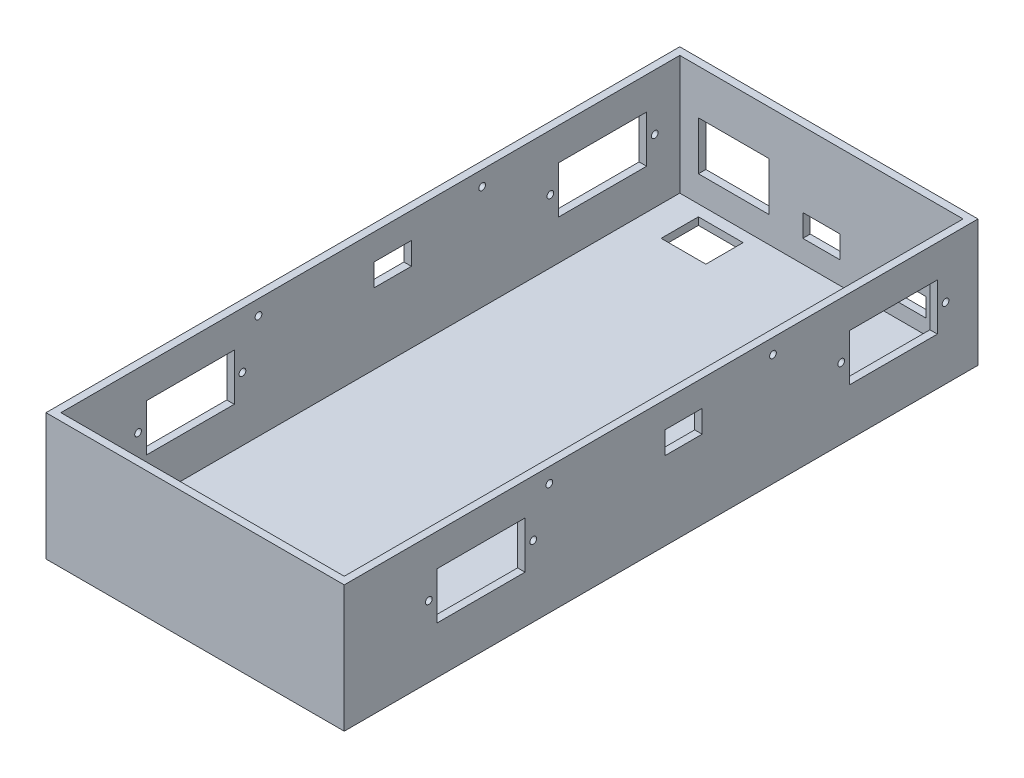
SolidWorks part; units mm, degrees
ref_plane "Front Plane" through (0, 0, 0) normal (0, 0, 1) x (1, 0, 0)
ref_plane "Top Plane" through (0, 0, 0) normal (0, 1, 0) x (1, 0, 0)
ref_plane "Right Plane" through (0, 0, 0) normal (1, 0, 0) x (0, 0, -1)
sketch "Sketch1" plane through (0, 0, 0) normal (0, 0, 1) x (1, 0, 0)
  line L1 (-40, 0) -> (40, 0)
  line L2 (-40, 0) -> (-40, 34)
  line L3 (-40, 34) -> (40, 34)
  line L4 (40, 0) -> (40, 34)
extrude "Boss-Extrude1" add sketch "Sketch1" along normal blind 170 from offset 85 offset against normal yes
sketch "Sketch2" plane through (0, 0, 0) normal (0, 0, 1) x (1, 0, 0)
  line L1 (-38, 2) -> (38, 2)
  line L2 (-38, 2) -> (-38, 40)
  line L3 (-38, 40) -> (38, 40)
  line L4 (38, 2) -> (38, 40)
extrude "Boss-Extrude2" add sketch "Sketch2" along normal blind 166 from offset 83 separate body offset against normal yes
combine bodies "Combine1" operation type subtract main body 101 bodies to subtract 102
sketch "Sketch3" plane through (0, 0, 0) normal (1, 0, 0) x (0, 0, -1)
  line L1 (-36.5, 12.7) -> (-60.1, 12.7)
  line L2 (-36.5, 12.7) -> (-36.5, 25.3)
  line L3 (-36.5, 25.3) -> (-60.1, 25.3)
  line L4 (-60.1, 12.7) -> (-60.1, 25.3)
extrude "Boss-Extrude3" add sketch "Sketch3" along normal blind 90 from offset 45 separate body offset against normal yes
combine bodies "Combine2" operation type subtract main body 103 bodies to subtract 104
sketch "Sketch4" plane through (0, 0, 0) normal (1, 0, 0) x (0, 0, -1)
  circle A0 centre (-34.3, 19) radius 0.9
extrude "Boss-Extrude4" add sketch "Sketch4" along normal blind 90 from offset 45 separate body offset against normal yes
combine bodies "Combine3" operation type subtract main body 105 bodies to subtract 106
sketch "Sketch5" plane through (0, 0, 0) normal (1, 0, 0) x (0, 0, -1)
  circle A0 centre (-62.3, 19) radius 0.9
extrude "Boss-Extrude5" add sketch "Sketch5" along normal blind 90 from offset 45 separate body offset against normal yes
combine bodies "Combine4" operation type subtract main body 107 bodies to subtract 108
sketch "Sketch6" plane through (0, 0, 0) normal (1, 0, 0) x (0, 0, -1)
  line L1 (74.1, 12.7) -> (50.5, 12.7)
  line L2 (74.1, 12.7) -> (74.1, 25.3)
  line L3 (74.1, 25.3) -> (50.5, 25.3)
  line L4 (50.5, 12.7) -> (50.5, 25.3)
extrude "Boss-Extrude6" add sketch "Sketch6" along normal blind 90 from offset 45 separate body offset against normal yes
combine bodies "Combine5" operation type subtract main body 109 bodies to subtract 110
sketch "Sketch7" plane through (0, 0, 0) normal (1, 0, 0) x (0, 0, -1)
  circle A0 centre (76.3, 19) radius 0.9
extrude "Boss-Extrude7" add sketch "Sketch7" along normal blind 90 from offset 45 separate body offset against normal yes
combine bodies "Combine6" operation type subtract main body 111 bodies to subtract 112
sketch "Sketch8" plane through (0, 0, 0) normal (1, 0, 0) x (0, 0, -1)
  circle A0 centre (48.3, 19) radius 0.9
extrude "Boss-Extrude8" add sketch "Sketch8" along normal blind 90 from offset 45 separate body offset against normal yes
combine bodies "Combine7" operation type subtract main body 113 bodies to subtract 114
sketch "Sketch9" plane through (0, 0, 0) normal (1, 0, 0) x (0, 0, -1)
  line L1 (11, 21) -> (1, 21)
  line L2 (11, 21) -> (11, 27)
  line L3 (11, 27) -> (1, 27)
  line L4 (1, 21) -> (1, 27)
extrude "Boss-Extrude9" add sketch "Sketch9" along normal blind 90 from offset 45 separate body offset against normal yes
combine bodies "Combine8" operation type subtract main body 115 bodies to subtract 116
sketch "Sketch10" plane through (0, 0, 0) normal (0, 0, 1) x (1, 0, 0)
  line L1 (-5, 8) -> (5, 8)
  line L2 (-5, 8) -> (-5, 14)
  line L3 (-5, 14) -> (5, 14)
  line L4 (5, 8) -> (5, 14)
extrude "Boss-Extrude10" add sketch "Sketch10" along normal blind 10 from offset 90 separate body offset against normal yes
combine bodies "Combine9" operation type subtract main body 117 bodies to subtract 118
sketch "Sketch11" plane through (0, 0, 0) normal (0, 0, 1) x (1, 0, 0)
  line L1 (18, 6) -> (28, 6)
  line L2 (18, 6) -> (18, 11)
  line L3 (18, 11) -> (28, 11)
  line L4 (28, 6) -> (28, 11)
extrude "Boss-Extrude11" add sketch "Sketch11" along normal blind 10 from offset 90 separate body offset against normal yes
combine bodies "Combine10" operation type subtract main body 119 bodies to subtract 120
sketch "Sketch12" plane through (0, 0, 0) normal (0, 0, 1) x (1, 0, 0)
  line L1 (-33, 9) -> (-14, 9)
  line L2 (-33, 9) -> (-33, 22)
  line L3 (-33, 22) -> (-14, 22)
  line L4 (-14, 9) -> (-14, 22)
extrude "Boss-Extrude12" add sketch "Sketch12" along normal blind 10 from offset 90 separate body offset against normal yes
combine bodies "Combine11" operation type subtract main body 121 bodies to subtract 122
sketch "Sketch13" plane through (0, 0, 0) normal (0, 0, 1) x (1, 0, 0)
  line L1 (-36, -1) -> (-24, -1)
  line L2 (-36, -1) -> (-36, 3)
  line L3 (-36, 3) -> (-24, 3)
  line L4 (-24, -1) -> (-24, 3)
extrude "Boss-Extrude13" add sketch "Sketch13" along normal blind 10 from offset 62 separate body
combine bodies "Combine12" operation type subtract main body 123 bodies to subtract 124
sketch "Sketch14" plane through (0, 0, 0) normal (0, 0, 1) x (1, 0, 0)
  line L1 (24, -1) -> (36, -1)
  line L2 (24, -1) -> (24, 3)
  line L3 (24, 3) -> (36, 3)
  line L4 (36, -1) -> (36, 3)
extrude "Boss-Extrude14" add sketch "Sketch14" along normal blind 10 from offset 62 separate body
combine bodies "Combine13" operation type subtract main body 125 bodies to subtract 126
sketch "Sketch15" plane through (0, 0, 0) normal (0, 0, 1) x (1, 0, 0)
  line L1 (-30, -1) -> (-18, -1)
  line L2 (-30, -1) -> (-30, 3)
  line L3 (-30, 3) -> (-18, 3)
  line L4 (-18, -1) -> (-18, 3)
extrude "Boss-Extrude15" add sketch "Sketch15" along normal blind 10 from offset 80 separate body offset against normal yes
combine bodies "Combine14" operation type subtract main body 127 bodies to subtract 128
sketch "Sketch16" plane through (0, 0, 0) normal (1, 0, 0) x (0, 0, -1)
  circle A0 centre (30, 30) radius 0.9
extrude "Boss-Extrude16" add sketch "Sketch16" along normal blind 90 from offset 45 separate body offset against normal yes
combine bodies "Combine15" operation type subtract main body 129 bodies to subtract 130
sketch "Sketch17" plane through (0, 0, 0) normal (1, 0, 0) x (0, 0, -1)
  circle A0 centre (-30, 30) radius 0.9
extrude "Boss-Extrude17" add sketch "Sketch17" along normal blind 90 from offset 45 separate body offset against normal yes
combine bodies "Combine16" operation type subtract main body 131 bodies to subtract 132
